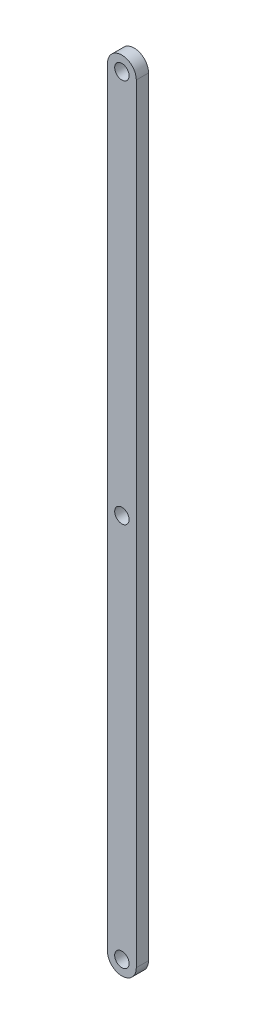
SolidWorks part; units mm, degrees
ref_plane "Front Plane" through (0, 0, 0) normal (0, 0, 1) x (1, 0, 0)
ref_plane "Top Plane" through (0, 0, 0) normal (0, 1, 0) x (1, 0, 0)
ref_plane "Right Plane" through (0, 0, 0) normal (1, 0, 0) x (0, 0, -1)
sketch "Model" plane through (0, 0, 0) normal (0, 0, 1) x (1, 0, 0)
  line L0 (0, 160) -> (0, 0) construction
  line L2 (-3, 160) -> (-3, 0)
  line L3 (0, 0) -> (0, 8.512) construction
  line L4 (3, 160) -> (3, 0)
  circle A0 centre (0, 0) radius 1.5
  arc A1 (-3, 0) -> (3, 0) centre (0, 0) ccw
  circle A2 centre (0, 80) radius 1.5
  circle A6 centre (0, 160) radius 1.5
  arc A7 (3, 160) -> (-3, 160) centre (0, 160) ccw
  dimension "D1" = 3
  dimension "D2" = 6
  dimension "D15" = 3
  dimension "D3" = 3
  dimension "D4" = 3
  dimension "D16" = 160
extrude "Boss-Extrude1" add sketch "Model" along normal blind 2.55
